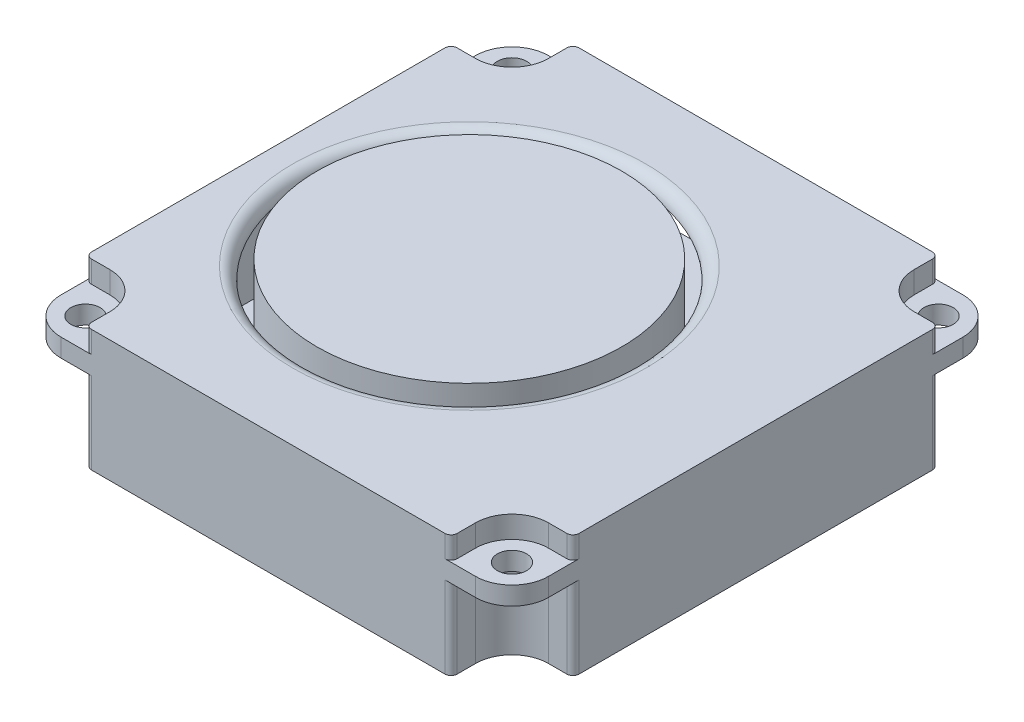
SolidWorks part; units mm, degrees
material "ABS"
ref_plane "正面" through (0, 0, 0) normal (0, 0, 1) x (1, 0, 0)
ref_plane "平面" through (0, 0, 0) normal (0, 1, 0) x (1, 0, 0)
ref_plane "右側面" through (0, 0, 0) normal (1, 0, 0) x (0, 0, -1)
sketch "ｽｹｯﾁ1" plane through (0, 0, 0) normal (0, 1, 0) x (1, 0, 0)
  line L1 (20, -20) -> (-20, -20)
  line L2 (20, -20) -> (20, 20)
  line L3 (20, 20) -> (-20, 20)
  line L4 (-20, -20) -> (-20, 20)
  line L5 (20, -20) -> (-20, 20) construction
  line L6 (20, 20) -> (-20, -20) construction
  point P0 (0, 0)
  dimension "D1" = 40
extrude "ﾎﾞｽ - 押し出し1" add sketch "ｽｹｯﾁ1" along normal mid plane 10
sketch "ｽｹｯﾁ2" plane through (0, 5, 0) normal (0, 1, 0) x (1, 0, 0)
  line L1 (20, 20) -> (15, 20)
  line L2 (20, 20) -> (20, 15)
  line L3 (20, 15) -> (15, 15)
  line L4 (15, 20) -> (15, 15)
  line L5 (0, 20) -> (0, 0) construction
  line L6 (20, 20) -> (-20, 20) construction
  line L7 (0, 0) -> (20, 0) construction
  line L8 (20, -20) -> (20, 20) construction
  line L9 (-15, 20) -> (-15, 15)
  line L10 (-20, 15) -> (-15, 15)
  line L11 (-20, 20) -> (-20, 15)
  line L12 (-20, 20) -> (-15, 20)
  line L13 (-20, -20) -> (-15, -20)
  line L14 (-20, -20) -> (-20, -15)
  line L15 (-20, -15) -> (-15, -15)
  line L16 (-15, -20) -> (-15, -15)
  line L17 (15, -20) -> (15, -15)
  line L18 (20, -15) -> (15, -15)
  line L19 (20, -20) -> (20, -15)
  line L20 (20, -20) -> (15, -20)
  dimension "D1" = 5
extrude "ｶｯﾄ - 押し出し1" cut sketch "ｽｹｯﾁ2" against normal blind 1.8
sketch "ｽｹｯﾁ4" plane through (0, -5, 0) normal (0, -1, 0) x (1, 0, 0)
  line L4 (15, -20) -> (20, -20)
  line L5 (15, -15) -> (15, -20)
  line L6 (20, -15) -> (15, -15)
  line L7 (20, -20) -> (20, -15)
  line L8 (15, -20) -> (20, -20)
  line L9 (15, -15) -> (15, -20)
  line L10 (20, -15) -> (15, -15)
  line L11 (20, -20) -> (20, -15)
  line L12 (15, 20) -> (15, 15)
  line L13 (15, 15) -> (20, 15)
  line L14 (20, 15) -> (20, 20)
  line L15 (20, 20) -> (15, 20)
  line L16 (15, 20) -> (15, 15)
  line L17 (15, 15) -> (20, 15)
  line L18 (20, 15) -> (20, 20)
  line L19 (20, 20) -> (15, 20)
  line L20 (-15, 20) -> (-20, 20)
  line L21 (-15, 15) -> (-15, 20)
  line L22 (-20, 15) -> (-15, 15)
  line L23 (-20, 20) -> (-20, 15)
  line L24 (-15, 20) -> (-20, 20)
  line L25 (-15, 15) -> (-15, 20)
  line L26 (-20, 15) -> (-15, 15)
  line L27 (-20, 20) -> (-20, 15)
  line L28 (-20, -15) -> (-20, -20)
  line L29 (-15, -15) -> (-20, -15)
  line L30 (-15, -20) -> (-15, -15)
  line L31 (-20, -20) -> (-15, -20)
  line L32 (-20, -15) -> (-20, -20)
  line L33 (-15, -15) -> (-20, -15)
  line L34 (-15, -20) -> (-15, -15)
  line L35 (-20, -20) -> (-15, -20)
  dimension "D1" = 0
  dimension "D2" = 0
  dimension "D3" = 0
  dimension "D4" = 0
extrude "ｶｯﾄ - 押し出し2" cut sketch "ｽｹｯﾁ4" against normal blind 6.7
fillet "ﾌｨﾚｯﾄ1" radius 3 12 edges at (-15, 4.1, -15) (15, 4.1, -15) (15, 4.1, 15) (-15, 4.1, 15) (-15, -1.65, 15) (-15, -1.65, -15) (15, -1.65, -15) (15, -1.65, 15) (20, 2.45, 20) (-20, 2.45, 20) (-20, 2.45, -20) (20, 2.45, -20)
hole_wizard "M2 すきま穴1" positions "ｽｹｯﾁ5" profile "ｽｹｯﾁ6" hole size "M2" standard "JIS" end condition through all
sketch "ｽｹｯﾁ5" plane through (0, 3.2, 0) normal (0, 1, 0) x (1, 0, 0)
  line L0 (-20, 0) -> (0, 0) construction
  line L1 (-20, 15) -> (-20, -15) construction
  line L3 (0, 0) -> (0, 20) construction
  line L4 (15, 20) -> (-15, 20) construction
  point P0 (-17.5, -17.5)
  point P9 (-17.5, 17.5)
  point P16 (17.5, 17.5)
  point P17 (17.5, -17.5)
  dimension "D1" = 35
  dimension "D2" = 35
sketch "ｽｹｯﾁ6" plane through (-17.5, 3.2, 17.5) normal (1, 0, 0) x (0, 0, 1)
  line L0 (0, 0) -> (0, 8.2)
  line L1 (0, 8.2) -> (1.2, 8.2)
  line L2 (1.2, 8.2) -> (1.2, 0)
  line L5 (1.2, 0) -> (0, 0)
  line L11 (0, -6.35) -> (0, 107.95) construction
  dimension "通し穴の直径" = 2.4
  dimension "通し穴の深さ" = 8.2
fillet "ﾌｨﾚｯﾄ2" radius 0.5 16 edges at (-15, 4.1, -20) (15, 4.1, -20) (20, 4.1, -15) (20, 4.1, 15) (-20, 4.1, -15) (15, 4.1, 20) (20, -1.65, -15) (15, -1.65, 20) (20, -1.65, 15) (15, -1.65, -20) (-15, -1.65, -20) (-20, -1.65, -15) (-15, -1.65, 20) (-20, -1.65, 15) (-20, 4.1, 15) (-15, 4.1, 20)
sketch "ｽｹｯﾁ8" plane through (0, 0, 0) normal (0, 1, 0) x (1, 0, 0)
  line L12 (-14, 19) -> (-14, 20)
  line L13 (14.5, 20) -> (-14.5, 20) construction
  line L14 (-14, 20) -> (14, 20)
  line L15 (14, 20) -> (14, 19)
  line L24 (19, 14) -> (18, 14)
  line L25 (19, -14) -> (19, 14)
  line L26 (18, -14) -> (19, -14)
  line L27 (14, -19) -> (14, -18)
  line L28 (-14, -19) -> (14, -19)
  line L29 (-14, -18) -> (-14, -19)
  line L30 (-19, -14) -> (-18, -14)
  line L31 (-19, 14) -> (-19, -14)
  line L32 (-18, 14) -> (-19, 14)
  line L33 (-14, 19) -> (-14, 18)
  line L34 (14, 19) -> (-14, 19)
  line L35 (14, 18) -> (14, 19)
  line L36 (19, 14) -> (18, 14)
  line L37 (19, -14) -> (19, 14)
  line L38 (18, -14) -> (19, -14)
  line L39 (14, -19) -> (14, -18)
  line L40 (-14, -19) -> (14, -19)
  line L41 (-14, -18) -> (-14, -19)
  line L42 (-19, -14) -> (-18, -14)
  line L43 (-19, 14) -> (-19, -14)
  line L44 (-18, 14) -> (-19, 14)
  line L45 (-14, 19) -> (-14, 18)
  line L47 (14, 18) -> (14, 19)
  arc A24 (18, -14) -> (14, -18) centre (18, -18) ccw
  arc A25 (-14, -18) -> (-18, -14) centre (-18, -18) ccw
  arc A26 (-18, 14) -> (-14, 18) centre (-18, 18) ccw
  arc A27 (14, 18) -> (18, 14) centre (18, 18) ccw
  arc A28 (18, -14) -> (14, -18) centre (18, -18) ccw
  arc A29 (-14, -18) -> (-18, -14) centre (-18, -18) ccw
  arc A30 (-18, 14) -> (-14, 18) centre (-18, 18) ccw
  arc A31 (14, 18) -> (18, 14) centre (18, 18) ccw
  point P3 (14, 19.0866)
  dimension "D1" = 1
extrude "ｶｯﾄ - 押し出し3" cut sketch "ｽｹｯﾁ8" against normal mid plane 8
sketch "ｽｹｯﾁ7" plane through (0, 5, 0) normal (0, -1, 0) x (1, 0, 0)
  line L0 (20, 14.5) -> (20, -14.5) construction
  line L1 (-3.5, 0) -> (0, 0) construction
  circle A0 centre (-3.5, 0) radius 13.5
  dimension "D1" = 27
  dimension "D2" = 23.5
extrude "ｶｯﾄ - 押し出し4" cut sketch "ｽｹｯﾁ7" along normal up to surface (9 mm away) up to face at (0, -4, -0.125)
fillet "ﾌｨﾚｯﾄ3" radius 1 1 edges at (-3.5, 5, -13.5)
sketch "ｽｹｯﾁ9" plane through (0, -4, 0) normal (0, 1, 0) x (1, 0, 0)
  circle A0 centre (-3.5, 0) radius 12.5
  dimension "D1" = 25
extrude "ﾎﾞｽ - 押し出し2" add sketch "ｽｹｯﾁ9" along normal offset from surface (9.5 mm away) 0.5 up to face at (-3.5, 5, 14.5) offset beyond the face yes
